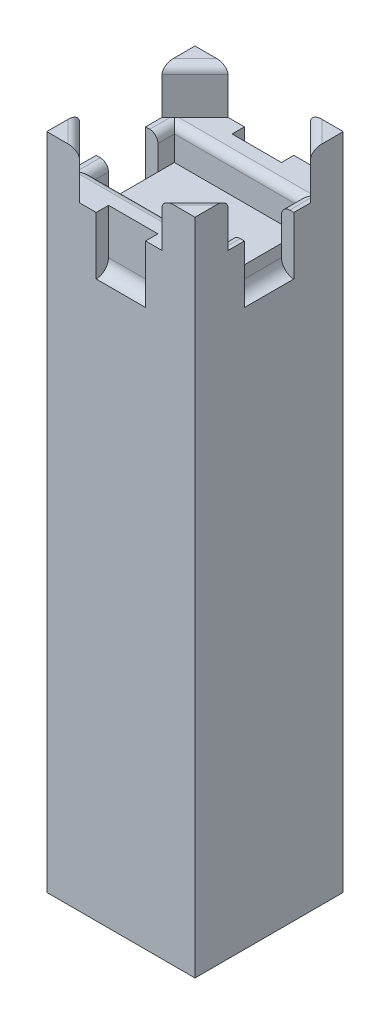
SolidWorks part; units mm, degrees
ref_plane "Front Plane" through (0, 0, 0) normal (0, 0, 1) x (1, 0, 0)
ref_plane "Top Plane" through (0, 0, 0) normal (0, 1, 0) x (1, 0, 0)
ref_plane "Right Plane" through (0, 0, 0) normal (1, 0, 0) x (0, 0, -1)
sketch "Sketch1" plane through (0, 0, 0) normal (0, 1, 0) x (1, 0, 0)
  line L1 (-9, -9) -> (9, -9)
  line L2 (-9, -9) -> (-9, 9)
  line L3 (-9, 9) -> (9, 9)
  line L4 (9, -9) -> (9, 9)
  line L5 (-9, -9) -> (9, 9) construction
  line L6 (-9, 9) -> (9, -9) construction
  point P0 (0, 0)
  dimension "D1" = 18
  dimension "D2" = 18
extrude "Boss-Extrude1" add sketch "Sketch1" along normal blind 80
sketch "Sketch2" plane through (0, 80, 0) normal (0, 1, 0) x (1, 0, 0)
  line L0 (9, -9) -> (9, 9) construction
  line L1 (-5, 9) -> (5, 9)
  line L2 (-9, 5) -> (-9, -5)
  line L3 (-5, -9) -> (5, -9)
  line L4 (9, 5) -> (9, -5)
  line L5 (-9, 9) -> (9, -9) construction
  line L6 (-9, -9) -> (9, 9) construction
  line L7 (-5, 9) -> (-9, 5)
  line L8 (5, 9) -> (9, 5)
  line L9 (5, -9) -> (9, -5)
  line L10 (-9, -5) -> (-5, -9)
  point P0 (0, 0)
extrude "Cut-Extrude1" cut sketch "Sketch2" against normal blind 5.5
sketch "Sketch3" plane through (0, 74.5, 0) normal (0, 1, 0) x (1, 0, 0)
  line L1 (-7.5, 5) -> (7.5, 5)
  line L2 (-7.5, 5) -> (-7.5, -5)
  line L3 (-7.5, -5) -> (7.5, -5)
  line L4 (7.5, 5) -> (7.5, -5)
  line L5 (-7.5, 5) -> (7.5, -5) construction
  line L6 (-7.5, -5) -> (7.5, 5) construction
  point P0 (0, 0)
  dimension "D1" = 10
  dimension "D2" = 15
extrude "Cut-Extrude2" cut sketch "Sketch3" against normal blind 4
fillet "Fillet1" radius 1 8 edges at (-7, 80, 7) (-7, 80, -7) (7, 80, -7) (7, 80, 7) (7.5, 74.5, 0) (0, 74.5, 5) (-7.5, 74.5, 0) (0, 74.5, -5)
sketch "Sketch4" plane through (0, 74.5, 0) normal (0, 1, 0) x (1, 0, 0)
  line L0 (5, 9) -> (-5, 9) construction
  line L1 (-3, 9) -> (3, 9)
  line L2 (-3, 9) -> (-3, 7.5)
  line L3 (-3, 7.5) -> (3, 7.5)
  line L4 (3, 9) -> (3, 7.5)
  line L5 (0, 0) -> (0, 7.5) construction
  line L6 (9, 3) -> (9, -3)
  line L7 (9, -3) -> (7.5, -3)
  line L8 (7.5, 3) -> (7.5, -3)
  line L9 (9, 3) -> (7.5, 3)
  line L10 (3, -9) -> (-3, -9)
  line L11 (-3, -9) -> (-3, -7.5)
  line L12 (3, -7.5) -> (-3, -7.5)
  line L13 (3, -9) -> (3, -7.5)
  line L14 (-9, -3) -> (-9, 3)
  line L15 (-9, 3) -> (-7.5, 3)
  line L16 (-7.5, -3) -> (-7.5, 3)
  line L17 (-9, -3) -> (-7.5, -3)
  point P24 (0, 0)
  dimension "D1" = 6
  dimension "D2" = 1.5
  dimension "D3" = 4
extrude "Cut-Extrude3" cut sketch "Sketch4" against normal blind 7
fillet "Fillet2" radius 1.5 4 edges at (0, 67.5, -7.5) (-7.5, 67.5, 0) (0, 67.5, 7.5) (7.5, 67.5, 0)
